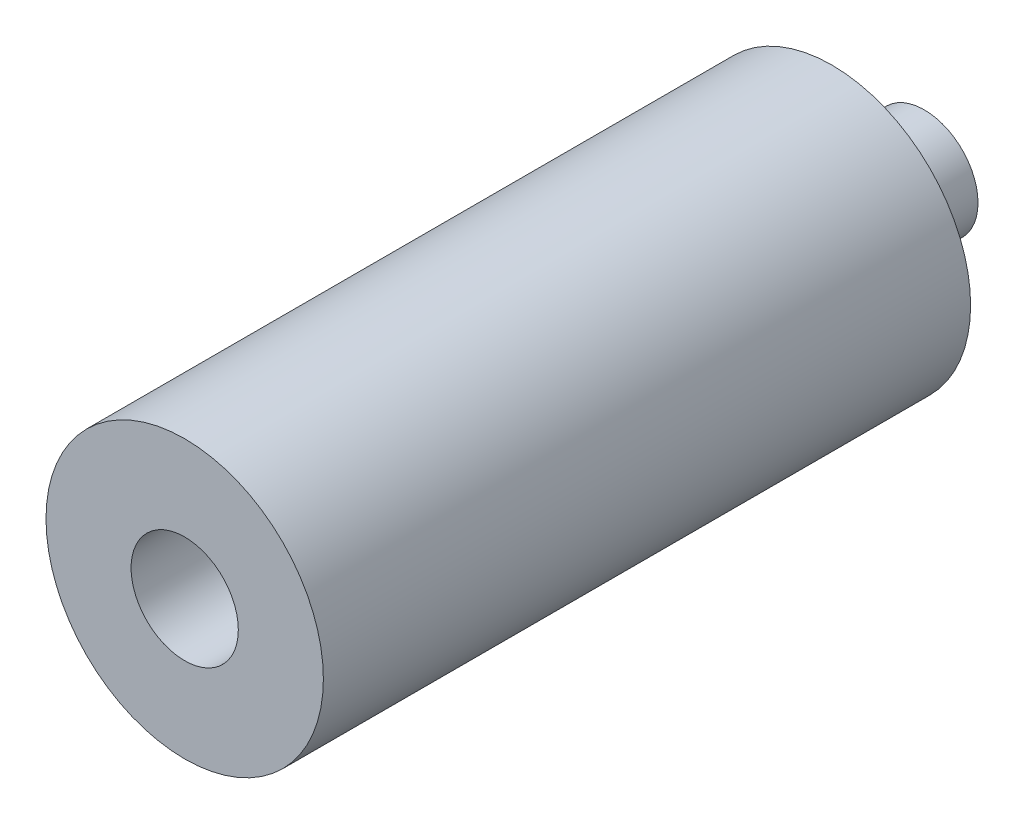
SolidWorks part; units mm, degrees
ref_plane "Front Plane" through (0, 0, 0) normal (0, 0, 1) x (1, 0, 0)
ref_plane "Top Plane" through (0, 0, 0) normal (0, 1, 0) x (1, 0, 0)
ref_plane "Right Plane" through (0, 0, 0) normal (1, 0, 0) x (0, 0, -1)
sketch "Sketch1" plane through (0, 0, 0) normal (0, 0, 1) x (1, 0, 0)
  circle A0 centre (0, 0) radius 2.9
  circle A1 centre (0, 0) radius 7.5
  dimension "D1" = 5.8
  dimension "D2" = 15
extrude "Boss-Extrude1" add sketch "Sketch1" along normal blind 35
extrude "Boss-Extrude2" add sketch "Sketch1<3>" against normal blind 5 contours A0
sketch "Sketch1<3>" plane through (0, 0, 0) normal (0, 0, 1) x (1, 0, 0) same geometry as "Sketch1"
